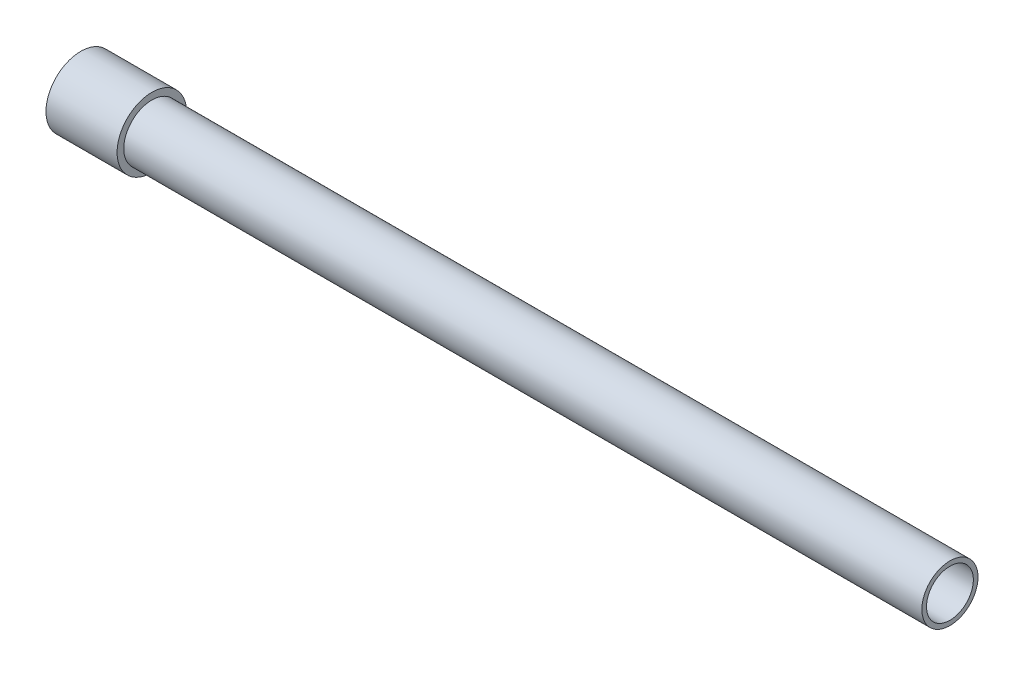
SolidWorks part; units mm, degrees
ref_plane "Front Plane" through (0, 0, 0) normal (0, 0, 1) x (1, 0, 0)
ref_plane "Top Plane" through (0, 0, 0) normal (0, 1, 0) x (1, 0, 0)
ref_plane "Right Plane" through (0, 0, 0) normal (1, 0, 0) x (0, 0, -1)
ref_axis "X-Axis" through (-88.99, 0, 0) along (1, 0, 0)
ref_axis "Y-Axis" through (0, 55, 0) along (0, -1, 0)
ref_axis "Z-Axis" through (0, 0, -88.99) along (0, 0, 1)
sketch "Sketch1" plane through (0, 0, 0) normal (1, 0, 0) x (0, 0, -1)
  circle A0 centre (0, 0) radius 9.4
  circle A1 centre (0, 0) radius 7.85
  dimension "D1" = 18.8
  dimension "D2" = 15.7
extrude "Boss-Extrude1" add sketch "Sketch1" along normal mid plane 291.1
sketch "Sketch2" plane through (-145.55, 0, 0) normal (-1, 0, 0) x (0, 0, 1)
  circle A2 centre (0, 0) radius 11.65
  circle A3 centre (0, 0) radius 9.4
  circle A4 centre (0, 0) radius 9.4
  dimension "D2" = 23.3
  dimension "D1" = 0
extrude "Boss-Extrude2" add sketch "Sketch2" against normal blind 23.8 separate body
